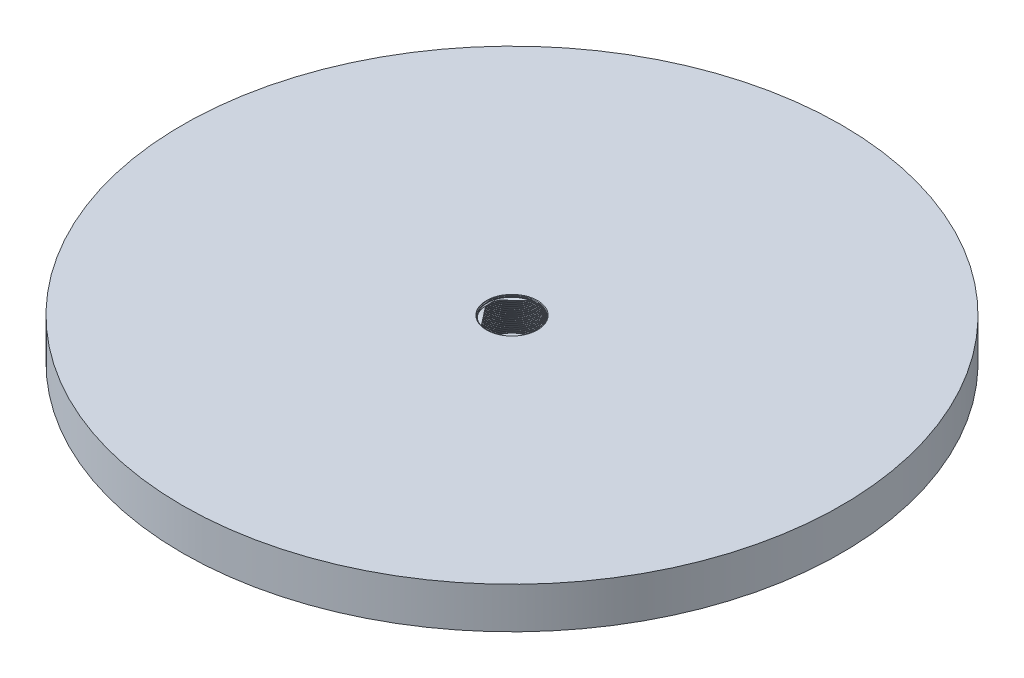
SolidWorks part; units mm, degrees
material "1023 Carbon Steel Sheet (SS)"
ref_plane "Front Plane" through (0, 0, 0) normal (0, 0, 1) x (1, 0, 0)
ref_plane "Top Plane" through (0, 0, 0) normal (0, 1, 0) x (1, 0, 0)
ref_plane "Right Plane" through (0, 0, 0) normal (1, 0, 0) x (0, 0, -1)
sketch "Sketch1" plane through (0, 0, 0) normal (0, 1, 0) x (1, 0, 0)
  circle A21 centre (0, 0) radius 400
  dimension "D1" = 800
extrude "Boss-Extrude1" add sketch "Sketch1" along normal mid plane 50
sketch "Sketch2" plane through (0, 25, 0) normal (0, 1, 0) x (1, 0, 0)
  circle A0 centre (0, 0) radius 30
  dimension "D1" = 60
extrude "Cut-Extrude1" cut sketch "Sketch2" against normal blind 40
chamfer "Chamfer1" distance 1 angle 45 1 edges at (0, 25, 30)
thread "Thread1" pitch 1.5 method cut profile "Thread Profile1" start angle 0, offset 5, length 0, pitch 2, diameter 60
ref_plane "Plane1" through (-30, 29, 0) normal (0, 0, 1) x (-1, 0, 0)
sketch "Thread Profile1" plane through (-30, 29, 0) normal (0, 0, 1) x (-1, 0, 0)
  line L0 (0, 0) -> (0, 1.5) construction
  line L1 (0, 0) -> (0.8119, 0.4687)
  line L2 (0.8119, 0.4687) -> (0.8119, 0.6562)
  line L3 (0.8119, 0.6562) -> (0, 1.125)
  line L4 (0.8119, 0.5625) -> (0, 0.5625) construction
  line L11 (0, 0) -> (0, 1.125)
  point P2 (0, 0)
  dimension "Pitch" = 1.5
  dimension "Profile_Angle" = 60
  dimension "Profile_Land" = 0.1875
  dimension "Profile_Height" = 0.8119
